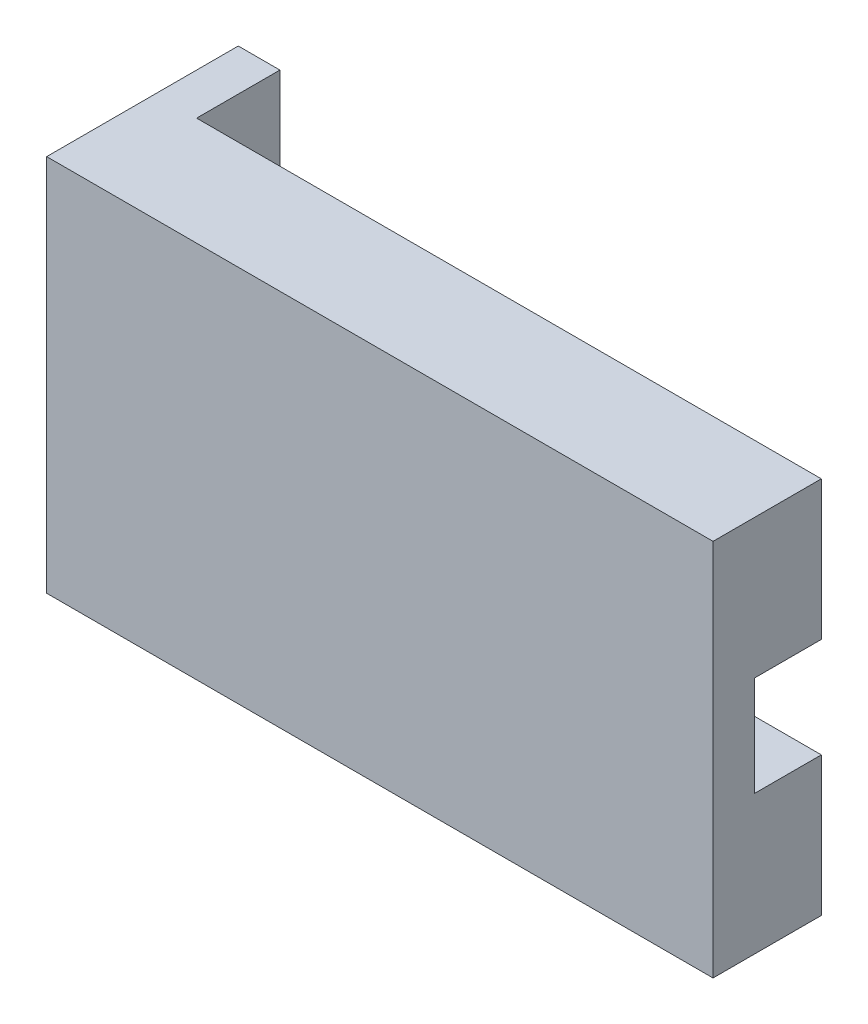
SolidWorks part; units mm, degrees
ref_plane "Front Plane" through (0, 0, 0) normal (0, 0, 1) x (1, 0, 0)
ref_plane "Top Plane" through (0, 0, 0) normal (0, 1, 0) x (1, 0, 0)
ref_plane "Right Plane" through (0, 0, 0) normal (1, 0, 0) x (0, 0, -1)
sketch "Sketch1" plane through (0, 0, 0) normal (0, 0, 1) x (1, 0, 0)
  line L1 (0, 0) -> (80, 0)
  line L2 (0, 0) -> (0, 45.4)
  line L3 (0, 45.4) -> (80, 45.4)
  line L4 (80, 0) -> (80, 45.4)
  dimension "D1" = 45.4
  dimension "D2" = 80
extrude "Boss-Extrude1" add sketch "Sketch1" along normal blind 13
sketch "Sketch2" plane through (0, 0, 0) normal (0, 0, -1) x (-1, 0, 0)
  line L0 (0, 0) -> (-80, 0) construction
  line L1 (0, 45.4) -> (-5, 45.4)
  line L2 (0, 45.4) -> (0, 0)
  line L3 (0, 0) -> (-5, 0)
  line L4 (-5, 45.4) -> (-5, 0)
  dimension "D1" = 5
extrude "Boss-Extrude2" add sketch "Sketch2" along normal blind 10
sketch "Sketch3" plane through (0, 0, 0) normal (0, 0, 1) x (1, 0, 0)
  line L0 (80, 0) -> (80, 45.4) construction
  line L1 (80, 28.7) -> (0, 28.7)
  line L2 (80, 28.7) -> (80, 16.7)
  line L3 (80, 16.7) -> (0, 16.7)
  line L4 (0, 28.7) -> (0, 16.7)
  line L5 (0, 0) -> (0, 45.4) construction
  line L6 (80, 22.7) -> (0, 22.7) construction
  point P10 (80, 22.7)
  dimension "D1" = 12
extrude "Cut-Extrude1" cut sketch "Sketch3" against normal through all and the other way blind 8
